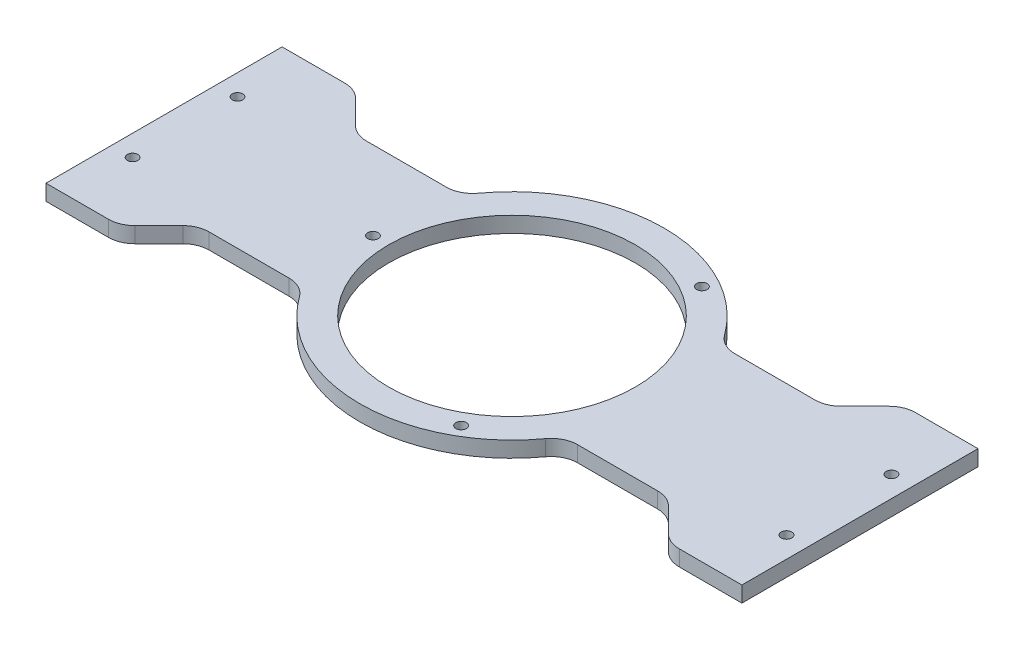
SolidWorks part; units mm, degrees
ref_plane "Front Plane" through (0, 0, 0) normal (0, 0, 1) x (1, 0, 0)
ref_plane "Top Plane" through (0, 0, 0) normal (0, 1, 0) x (1, 0, 0)
ref_plane "Right Plane" through (0, 0, 0) normal (1, 0, 0) x (0, 0, -1)
sketch "Sketch2" plane through (0, 0, 0) normal (0, 1, 0) x (1, 0, 0)
  line L0 (24.8193, 15) -> (44.8193, 15)
  line L1 (24.8193, -15) -> (44.8193, -15)
  line L2 (44.8193, 15) -> (52.3193, 22.5)
  line L3 (52.3193, 22.5) -> (66.3193, 22.5)
  line L4 (66.3193, 22.5) -> (66.3193, -22.5)
  line L5 (66.3193, -22.5) -> (52.3193, -22.5)
  line L6 (52.3193, -22.5) -> (44.8193, -15)
  line L7 (-55, 0) -> (55, 0) construction
  circle A0 centre (0, 0) radius 23 construction
  circle A2 centre (0, 0) radius 23.5
  circle A3 centre (62.3193, 10) radius 1
  circle A4 centre (62.3193, -10) radius 1
  circle A5 centre (0, 0) radius 29
  point P13 (66.3193, 0)
  dimension "D1" = 46
  dimension "D12" = 2
  dimension "D3" = 58
  dimension "D2" = 0.5
  dimension "D4" = 30
  dimension "D5" = 20
  dimension "D6" = 45
  dimension "D7" = 14
  dimension "D8" = 45
  dimension "D9" = 45
  dimension "D10" = 4
  dimension "D11" = 10
extrude "Boss-Extrude1" add sketch "Sketch2" along normal blind 3 contours A5 A2 region at (27.1452, 0, -7.5656)
extrude "Boss-Extrude2" add sketch "Sketch2<3>" along normal up to surface (3 mm away) contours A5 L1 L6 L5 L4 L3 L2 L0 A4 A3 region at (48.8368, 0, 0) up to face at (0, 3, 23.5)
sketch "Sketch2<3>" plane through (0, 0, 0) normal (0, 1, 0) x (1, 0, 0) same geometry as "Sketch2"
fillet "Fillet1" radius 5 6 edges at (24.8193, 1.5, -15) (24.8193, 1.5, 15) (52.3193, 1.5, 22.5) (52.3193, 1.5, -22.5) (44.8193, 1.5, -15) (44.8193, 1.5, 15)
sketch "Sketch3" plane through (0, 3, 0) normal (0, 1, 0) x (1, 0, 0)
  line L0 (0, 0) -> (13.25, 22.9497) construction
  circle A0 centre (13.25, 22.9497) radius 1
  point P2 (-1.6267, 2.6757)
  dimension "D3" = 2
  dimension "D1" = 26.5
  dimension "D2" = 60
extrude "Cut-Extrude1" cut sketch "Sketch3" against normal up to surface (3 mm away) contours A0 up to face at (0, 0, 23.5)
pattern_circular "CirPattern1" count 3 over 360 about axis through (0, 3, 0) along (0, 1, 0) of "Cut-Extrude1"
mirror "Mirror1" about plane through (0, 0, 0) normal (1, 0, 0) of "Fillet1", "Boss-Extrude2"
equation "\"motor-dia\" = 46"
equation "\"motor-holes-rad\" = 15"
equation "\"motor-height\" = 21"
equation "\"motor-case-thickness\" = 2"
equation "\"D1@Sketch2\"=\"motor-dia\""
